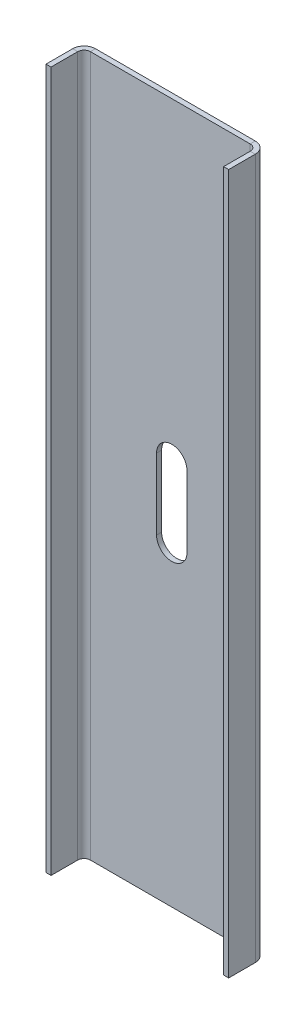
SolidWorks part; units mm, degrees
note: The reader was unsure of these and kept them because the rebuilt part matched: flange length of "Edge-Flange1", "Edge-Flange2".
material "Galvanized Steel"
ref_plane "Front Plane" through (0, 0, 0) normal (0, 0, 1) x (1, 0, 0)
ref_plane "Top Plane" through (0, 0, 0) normal (0, 1, 0) x (1, 0, 0)
ref_plane "Right Plane" through (0, 0, 0) normal (1, 0, 0) x (0, 0, -1)
sketch "Sketch1" plane through (0, 0, 0) normal (0, 0, 1) x (1, 0, 0)
  line L1 (55.8, 173.625) -> (-16.2, 173.625)
  line L2 (55.8, 173.625) -> (55.8, -102.375)
  line L3 (55.8, -102.375) -> (-16.2, -102.375)
  line L4 (-16.2, 173.625) -> (-16.2, -102.375)
  dimension "D1" = 72
  dimension "D2" = 276
base flange "Base-Flange1" sketch "Sketch1" thickness 2 reverse thickness direction no parameters "D1"=0.5
edge flange "Edge-Flange1" sketch "Sketch8" flange angle 90 flange length 15 flange position material inside bend radius 2.5 thickness 2 relief obround parameters "D6"=10
sketch "Sketch8" plane through (55.8, 0, 0) normal (1, 0, 0) x (0, 1, 0)
  line L2 (-102.375, 0) -> (-102.375, 13)
  line L3 (-102.375, 13) -> (173.625, 13)
  line L4 (173.625, 13) -> (173.625, 0)
  line L5 (-102.375, 0) -> (173.625, 0) construction
  line L6 (-102.375, 0) -> (173.625, 0)
bend "EdgeBend1" bend radius 2.5 bend angle 90 parameters "D5"=1
edge flange "Edge-Flange2" sketch "Sketch11" flange angle 90 flange length 15 flange position material inside bend radius 2.5 thickness 2 relief obround parameters "D6"=10
sketch "Sketch11" plane through (-16.2, 0, 0) normal (-1, 0, 0) x (0, -1, 0)
  line L2 (-173.625, 0) -> (-173.625, 13)
  line L3 (-173.625, 13) -> (102.375, 13)
  line L4 (102.375, 13) -> (102.375, 0)
  line L5 (-173.625, 0) -> (102.375, 0) construction
  line L6 (-173.625, 0) -> (102.375, 0)
bend "EdgeBend2" bend radius 2.5 bend angle 90 parameters "D5"=2
sketch "Sketch12" plane through (0, 0, 0) normal (0, 0, 1) x (1, 0, 0)
  line L0 (20.3826, 49.625) -> (20.3826, 21.625) construction
  line L1 (26.3826, 49.625) -> (26.3826, 21.625)
  line L2 (14.3826, 49.625) -> (14.3826, 21.625)
  line L3 (51.3, 173.625) -> (-11.7, 173.625) construction
  arc A0 (26.3826, 49.625) -> (14.3826, 49.625) centre (20.3826, 49.625) ccw
  arc A1 (14.3826, 21.625) -> (26.3826, 21.625) centre (20.3826, 21.625) ccw
  point P2 (20.3826, 35.625)
  point P9 (20.3826, 15.625)
  point P10 (20.3826, 55.625)
  dimension "D2" = 6
  dimension "D1" = 138
  dimension "D3" = 40
extrude "Cut-Extrude1" cut sketch "Sketch12" along normal through all both and the other way through all normal cut yes
sketch "Bend-Lines1" [suppressed] plane through (0, 0, 0) normal (0, 1, 0) x (1, 0, 0)
sketch "Bounding-Box1" [suppressed] plane through (0, 0, 0) normal (0, 1, 0) x (1, 0, 0)
sheet metal parameters "Sheet-Metal1" thickness 2 parameters "D1"=0.5
flat pattern "Flat-Pattern1" [suppressed]
sketch "Bend-Lines2" plane through (0, 0, 0) normal (0, 1, 0) x (1, 0, 0)
sketch3d "Bounding-Box2" [suppressed]
  line L0 (-55.8, 173.625, 0) -> (-55.8, -102.375, 0) construction
  line L1 (16.2, 173.625, 0) -> (16.2, -102.375, 0) construction
  line L2 (-55.8, 173.625, 0) -> (16.2, 173.625, 0) construction
  line L3 (-55.8, -102.375, 0) -> (16.2, -102.375, 0) construction
sheet metal parameters "Sheet-Metal2" thickness 2 parameters "D1"=0.5
flat pattern "Flat-Pattern1"
sketch "Bend-Lines2" plane through (0, 0, 0) normal (0, 0, 1) x (1, 0, 0)
  line L0 (54.4781, -102.375) -> (54.4781, 173.625) construction
  line L1 (54.4781, -102.375) -> (54.4781, 173.625) construction
sketch3d "Bounding-Box2" [suppressed]
  line L0 (63.1562, 173.625, 0) -> (63.1562, -102.375, 0) construction
  line L1 (-16.2, 173.625, 0) -> (-16.2, -102.375, 0) construction
  line L2 (63.1562, 173.625, 0) -> (-16.2, 173.625, 0) construction
  line L3 (63.1562, -102.375, 0) -> (-16.2, -102.375, 0) construction
bend of the flat pattern "Flatten-<EdgeBend1>1"
sheet metal parameters "Sheet-Metal3" thickness 2 parameters "D1"=0.5
flat pattern "Flat-Pattern1"
sketch "Bend-Lines2" plane through (0, 0, 0) normal (0, 0, 1) x (1, 0, 0)
  line L0 (54.4781, -102.375) -> (54.4781, 173.625) construction
  line L1 (54.4781, -102.375) -> (54.4781, 173.625) construction
  line L2 (-14.8781, 173.625) -> (-14.8781, -102.375) construction
  line L3 (-14.8781, 173.625) -> (-14.8781, -102.375) construction
sketch3d "Bounding-Box2" [suppressed]
  line L0 (63.1562, 173.625, 0) -> (63.1562, -102.375, 0) construction
  line L1 (-25.5562, 173.625, 0) -> (-25.5562, -102.375, 0) construction
  line L2 (63.1562, 173.625, 0) -> (-25.5562, 173.625, 0) construction
  line L3 (63.1562, -102.375, 0) -> (-25.5562, -102.375, 0) construction
bend of the flat pattern "Flatten-<EdgeBend1>1"
bend of the flat pattern "Flatten-<EdgeBend2>1"
sheet metal parameters "Sheet-Metal4" thickness 2 parameters "D1"=0.5
flat pattern "Flat-Pattern1"
sketch "Bend-Lines2" plane through (0, 0, 0) normal (0, 0, 1) x (1, 0, 0)
  line L0 (54.0489, -102.375) -> (54.0489, 173.625) construction
  line L1 (54.0489, -102.375) -> (54.0489, 173.625) construction
  line L2 (-14.4489, 173.625) -> (-14.4489, -102.375) construction
  line L3 (-14.4489, 173.625) -> (-14.4489, -102.375) construction
sketch3d "Bounding-Box2" [suppressed]
  line L0 (67.2978, 173.625, 0) -> (67.2978, -102.375, 0) construction
  line L1 (-27.6978, 173.625, 0) -> (-27.6978, -102.375, 0) construction
  line L2 (67.2978, 173.625, 0) -> (-27.6978, 173.625, 0) construction
  line L3 (67.2978, -102.375, 0) -> (-27.6978, -102.375, 0) construction
bend of the flat pattern "Flatten-<EdgeBend1>1"
bend of the flat pattern "Flatten-<EdgeBend2>1"
